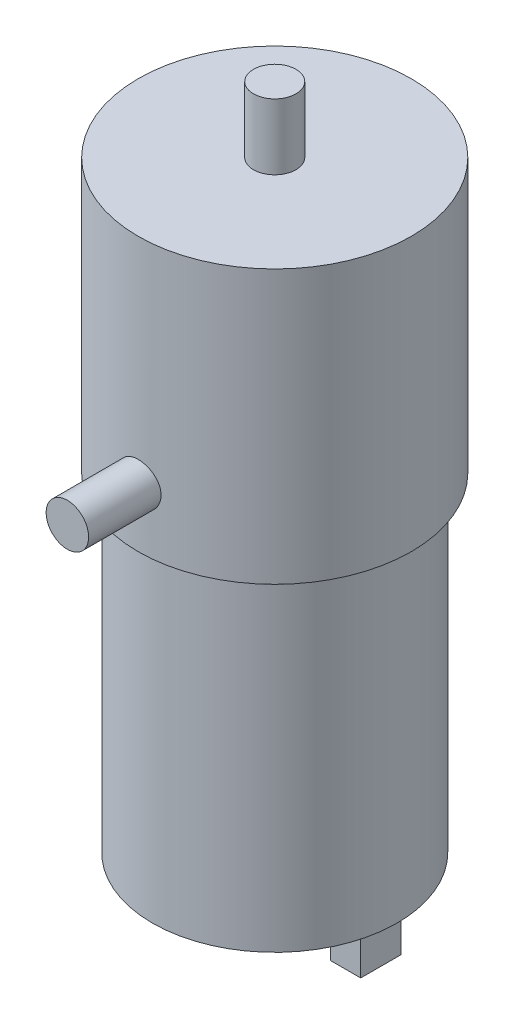
SolidWorks part; units mm, degrees
ref_plane "Plan de face" through (0, 0, 0) normal (0, 0, 1) x (1, 0, 0)
ref_plane "Plan de dessus" through (0, 0, 0) normal (0, 1, 0) x (1, 0, 0)
ref_plane "Plan de droite" through (0, 0, 0) normal (1, 0, 0) x (0, 0, -1)
sketch "Esquisse1" plane through (0, 0, 0) normal (0, 0, 1) x (1, 0, 0)
  line L0 (0, 44.1715) -> (0, -58.4059) construction
  line L1 (0, 33.5) -> (0, -32.5)
  line L2 (0, -32.5) -> (12.1, -32.5)
  line L3 (12.1, -32.5) -> (12.1, -1)
  line L4 (11.1, 0) -> (13.5, 0)
  line L5 (13.5, 0) -> (13.5, 27)
  line L6 (13.5, 27) -> (2.1, 27)
  line L7 (2.1, 27) -> (2.1, 33.5)
  line L8 (2.1, 33.5) -> (0, 33.5)
  arc A0 (12.1, -1) -> (11.1, 0) centre (11.1, -1) ccw
  point P14 (9.1942, 0.1994)
  point P15 (12.1, -2.4949)
  point P16 (0, 0)
  dimension "D7" = 1
  dimension "D1" = 27
  dimension "D2" = 59.5
  dimension "D3" = 6.5
  dimension "D4" = 4.2
  dimension "D5" = 27
  dimension "D6" = 24.2
revolve "Révolution1" add sketch "Esquisse1" angle 360 about L0
sketch "Esquisse2" plane through (0, 0, 0) normal (0, 0, 1) x (1, 0, 0)
  line L0 (13.5, 27) -> (-13.5, 27) construction
  circle A0 centre (0, 5.8) radius 2.1
  point P4 (0, 0)
  dimension "D1" = 4.2
  dimension "D2" = 21.2
extrude "Boss.-Extru.1" add sketch "Esquisse2" along normal blind 20.5
sketch "Esquisse3" plane through (0, -32.5, 0) normal (0, -1, 0) x (1, 0, 0)
  line L0 (-7.5, 0) -> (7.5, 0) construction
  line L1 (-10.5, 2) -> (-7.5, 2)
  line L2 (-10.5, 2) -> (-10.5, -2)
  line L3 (-10.5, -2) -> (-7.5, -2)
  line L4 (-7.5, 2) -> (-7.5, -2)
  line L5 (7.5, 2) -> (10.5, 2)
  line L6 (7.5, 2) -> (7.5, -2)
  line L7 (7.5, -2) -> (10.5, -2)
  line L8 (10.5, 2) -> (10.5, -2)
  dimension "D1" = 15
  dimension "D2" = 21
  dimension "D3" = 4
extrude "Boss.-Extru.2" add sketch "Esquisse3" along normal blind 4.5
ref_point "Point1"
